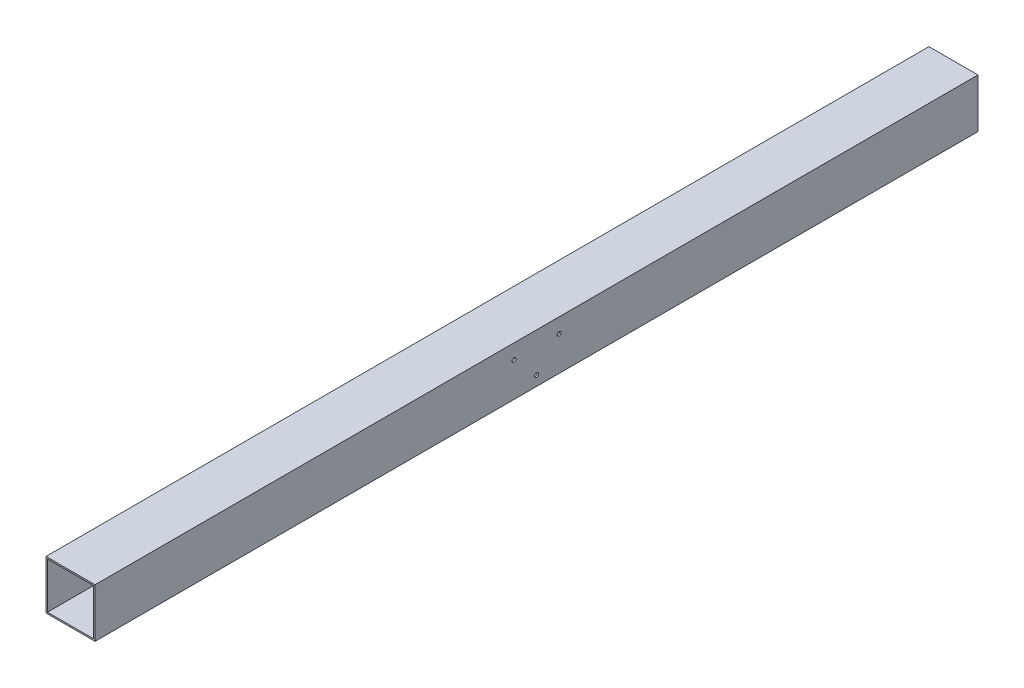
SolidWorks part; units mm, degrees
material "6061 Alloy"
ref_plane "Front Plane" through (0, 0, 0) normal (0, 0, 1) x (1, 0, 0)
ref_plane "Top Plane" through (0, 0, 0) normal (0, 1, 0) x (1, 0, 0)
ref_plane "Right Plane" through (0, 0, 0) normal (1, 0, 0) x (0, 0, -1)
sketch "Sketch1" plane through (0, 0, 0) normal (0, 0, 1) x (1, 0, 0)
  line L1 (-23.5, 23.5) -> (23.5, 23.5)
  line L2 (-23.5, 23.5) -> (-23.5, -23.5)
  line L3 (-23.5, -23.5) -> (23.5, -23.5)
  line L4 (23.5, 23.5) -> (23.5, -23.5)
  line L5 (-23.5, 23.5) -> (23.5, -23.5) construction
  line L6 (-23.5, -23.5) -> (23.5, 23.5) construction
  line L7 (-25, 25) -> (25, 25)
  line L8 (-25, 25) -> (-25, -25)
  line L9 (-25, -25) -> (25, -25)
  line L10 (25, 25) -> (25, -25)
  line L11 (-25, 25) -> (25, -25) construction
  line L12 (-25, -25) -> (25, 25) construction
  point P0 (0, 0)
  point P6 (0, 0)
  dimension "D1" = 50
  dimension "D2" = 47
  dimension "D3" = 50
  dimension "D4" = 47
extrude "Boss-Extrude1" add sketch "Sketch1" along normal blind 900
sketch "Sketch2" plane through (25, 0, 0) normal (1, 0, 0) x (0, 0, -1)
  line L0 (-900, -25) -> (0, -25) construction
  line L1 (-450, -25) -> (-450, 25) construction
  line L2 (-900, 25) -> (0, 25) construction
  line L3 (0, -25) -> (0, 25) construction
  circle A0 centre (-450, -15) radius 2
  circle A1 centre (-427, 10) radius 2
  circle A2 centre (-473, 10) radius 2
  point P0 (-450, -25)
  dimension "D4" = 4
  dimension "D1" = 10
  dimension "D2" = 25
  dimension "D3" = 23
  dimension "D5" = 450
extrude "Cut-Extrude1" cut sketch "Sketch2" against normal blind 59
sketch "Sketch5" plane through (25, 0, 0) normal (1, 0, 0) x (0, 0, -1)
  line L0 (-900, -25) -> (0, -25) construction
  line L1 (-900, 25) -> (0, 25) construction
  line L2 (-900, -25) -> (-900, 25) construction
  line L3 (-849.5, 25) -> (-849.5, -25) construction
  circle A0 centre (-882.5, 11) radius 3
  circle A2 centre (-882.5, -11) radius 3
  circle A3 centre (-816.5, -11) radius 3
  circle A4 centre (-816.5, 11) radius 3
  dimension "D4" = 6
  dimension "D6" = 6
  dimension "D1" = 33
  dimension "D2" = 14
  dimension "D3" = 14
  dimension "D7" = 17.5
ref_plane "Plane1" through (0, 0, 450) normal (0, 0, 1) x (1, 0, 0)
sketch "Sketch6" plane through (0, 25, 0) normal (0, 1, 0) x (1, 0, 0)
  line L0 (0, -694.2275) -> (0, -739.8525) construction
  line L2 (-27.5, -450) -> (27.5, -450) construction
  circle A0 centre (0, -694.2275) radius 3.125
  circle A1 centre (0, -739.8525) radius 3.125
  circle A2 centre (0, -717.04) radius 5
  point P8 (0, -717.04)
  dimension "D1" = 6.25
  dimension "D2" = 6.25
  dimension "D5" = 10
  dimension "D3" = 45.625
  dimension "D4" = 267.04
